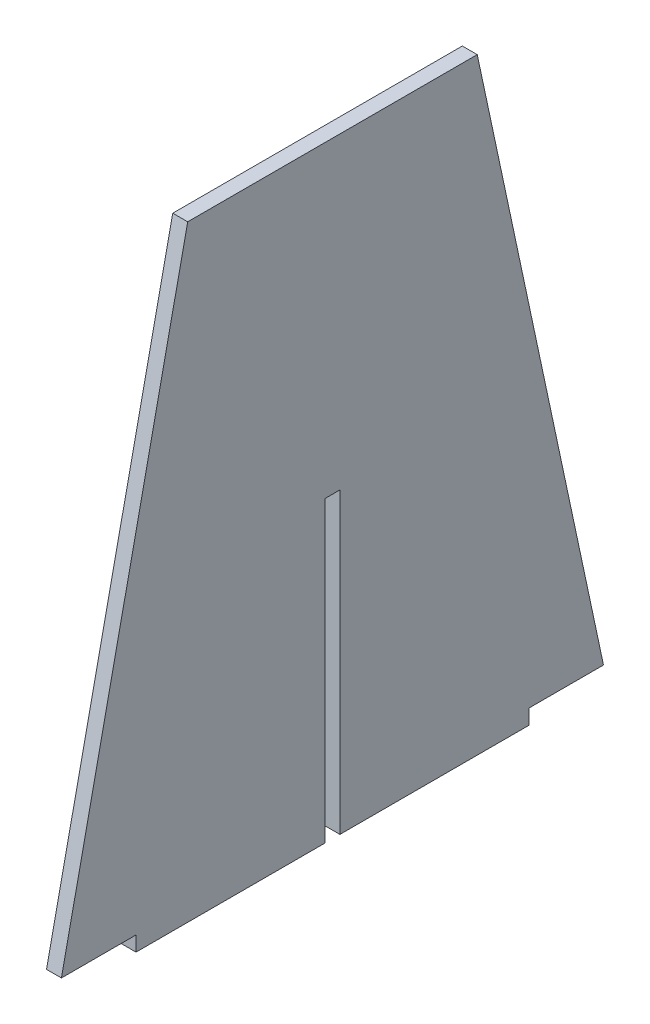
SolidWorks part; units mm, degrees
ref_plane "Спереди" through (0, 0, 0) normal (0, 0, 1) x (1, 0, 0)
ref_plane "Сверху" through (0, 0, 0) normal (0, 1, 0) x (1, 0, 0)
ref_plane "Справа" through (0, 0, 0) normal (1, 0, 0) x (0, 0, -1)
sketch "Эскиз1" plane through (0, 0, 0) normal (1, 0, 0) x (0, 0, -1)
  line L0 (0, 0) -> (0, 119) construction
  line L6 (54.5, 0) -> (29.1133, 119)
  line L7 (54.5, 0) -> (39.5, 0)
  line L8 (39.5, 0) -> (39.5, -3)
  line L9 (39.5, -3) -> (1.5, -3)
  line L10 (-39.5, -3) -> (-1.5, -3)
  line L11 (-39.5, 0) -> (-39.5, -3)
  line L12 (-54.5, 0) -> (-39.5, 0)
  line L13 (-54.5, 0) -> (-29.1133, 119)
  line L14 (-1.5, 57) -> (-1.5, -3)
  line L15 (1.5, -3) -> (1.5, 57)
  line L16 (29.1133, 119) -> (-29.1133, 119)
  line L17 (1.5, 57) -> (-1.5, 57)
  point P16 (0, 75)
extrude "Бобышка-Вытянуть1" add sketch "Эскиз1" along normal blind 3
